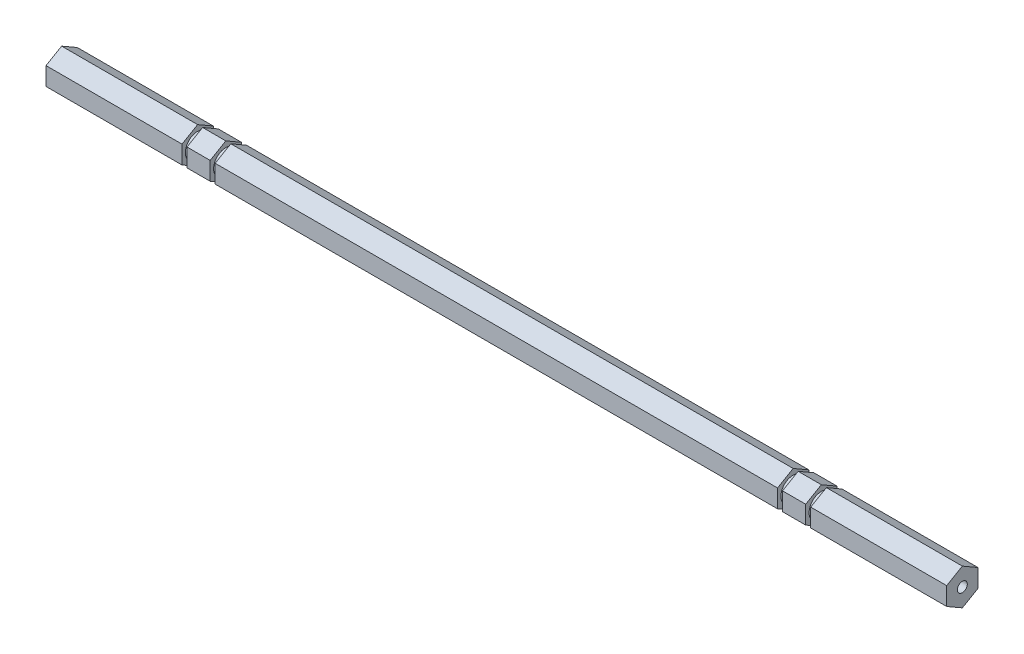
SolidWorks part; units mm, degrees
material "6061-T6 (SS)"
ref_plane "Front" through (0, 0, 0) normal (0, 0, 1) x (1, 0, 0)
ref_plane "Top" through (0, 0, 0) normal (0, 1, 0) x (1, 0, 0)
ref_plane "Right" through (0, 0, 0) normal (1, 0, 0) x (0, 0, -1)
ref_axis "Axis1" through (-80.9, 0, 0) along (1, 0, 0)
sketch "Sketch1" plane through (0, 0, 0) normal (1, 0, 0) x (0, 0, -1)
  line L1 (0, 7.3323) -> (-6.35, 3.6662)
  line L2 (-6.35, 3.6662) -> (-6.35, -3.6662)
  line L3 (-6.35, -3.6662) -> (0, -7.3323)
  line L4 (0, -7.3323) -> (6.35, -3.6662)
  line L5 (6.35, -3.6662) -> (6.35, 3.6662)
  line L6 (6.35, 3.6662) -> (0, 7.3323)
  circle A0 centre (0, 0) radius 6.35 construction
  dimension "D1" = 12.7
extrude "Boss-Extrude1" add sketch "Sketch1" along normal up to surface (365.125 mm away)
hole_wizard "#10-32 Tapped Hole1" positions "Sketch2" profile "Sketch3" tap size "#10-32" standard "ANSI Inch"
sketch "Sketch2" plane through (365.125, 0, 0) normal (1, 0, 0) x (0, 0, -1)
  point P0 (0, 0)
sketch "Sketch3" plane through (365.125, 0, 0) normal (0, 1, 0) x (0, 0, -1)
  line L0 (0, 0) -> (0, 13.2529)
  line L1 (0, 13.2529) -> (2.0193, 12.0396)
  line L2 (2.0193, 12.0396) -> (2.0193, 0)
  line L5 (2.0193, 0) -> (0, 0)
  line L10 (0, 13.2529) -> (-2.0193, 12.0396) construction
  line L11 (0, -6.35) -> (0, 107.95) construction
  dimension "Tap Drill Dia." = 4.0386
  dimension "Tap Drill Depth" = 12.0396
  dimension "Drill Angle" = 118
cosmetic thread "Hole Thread1" parameters "D1"=9.652, "D2"=4.826
hole_wizard "#10-32 Tapped Hole2" positions "Sketch4" profile "Sketch5" tap size "#10-32" standard "ANSI Inch"
sketch "Sketch4" plane through (0, 0, 0) normal (-1, 0, 0) x (0, 0, 1)
  point P0 (0, 0)
sketch "Sketch5" plane through (0, 0, 0) normal (0, 1, 0) x (0, 0, 1)
  line L0 (0, 0) -> (0, 13.2529)
  line L1 (0, 13.2529) -> (2.0193, 12.0396)
  line L2 (2.0193, 12.0396) -> (2.0193, 0)
  line L5 (2.0193, 0) -> (0, 0)
  line L10 (0, 13.2529) -> (-2.0193, 12.0396) construction
  line L11 (0, -6.35) -> (0, 107.95) construction
  dimension "Tap Drill Dia." = 4.0386
  dimension "Tap Drill Depth" = 12.0396
  dimension "Drill Angle" = 118
cosmetic thread "Hole Thread2" parameters "D1"=9.652, "D2"=4.826
sketch "Sketch6" plane through (0, 0, 0) normal (0, 0, 1) x (1, 0, 0)
  line L0 (365.125, 7.3323) -> (0, 7.3323) construction
  line L1 (57.15, 7.3323) -> (55.118, 7.3323)
  line L2 (57.15, 7.3323) -> (57.15, 4.9784)
  line L3 (57.15, 4.9784) -> (55.118, 4.9784)
  line L4 (55.118, 7.3323) -> (55.118, 4.9784)
  line L5 (0, 0) -> (37.1847, 0) construction
  line L6 (68.58, 7.3323) -> (66.548, 7.3323)
  line L7 (68.58, 7.3323) -> (68.58, 4.9784)
  line L8 (68.58, 4.9784) -> (66.548, 4.9784)
  line L9 (66.548, 7.3323) -> (66.548, 4.9784)
  line L10 (0, 3.6662) -> (0, 7.3323) construction
  line L11 (182.5625, 7.3323) -> (182.5625, 25.2168) construction
  line L12 (298.577, 7.3323) -> (298.577, 4.9784)
  line L13 (296.545, 4.9784) -> (298.577, 4.9784)
  line L14 (296.545, 7.3323) -> (296.545, 4.9784)
  line L15 (296.545, 7.3323) -> (298.577, 7.3323)
  line L16 (310.007, 7.3323) -> (310.007, 4.9784)
  line L17 (307.975, 4.9784) -> (310.007, 4.9784)
  line L18 (307.975, 7.3323) -> (307.975, 4.9784)
  line L19 (307.975, 7.3323) -> (310.007, 7.3323)
  dimension "D1" = 9.9568
  dimension "D2" = 2.032
  dimension "D3" = 11.43
  dimension "D4" = 57.15
revolve "Cut-Revolve1" cut sketch "Sketch6" angle 360 about L5
